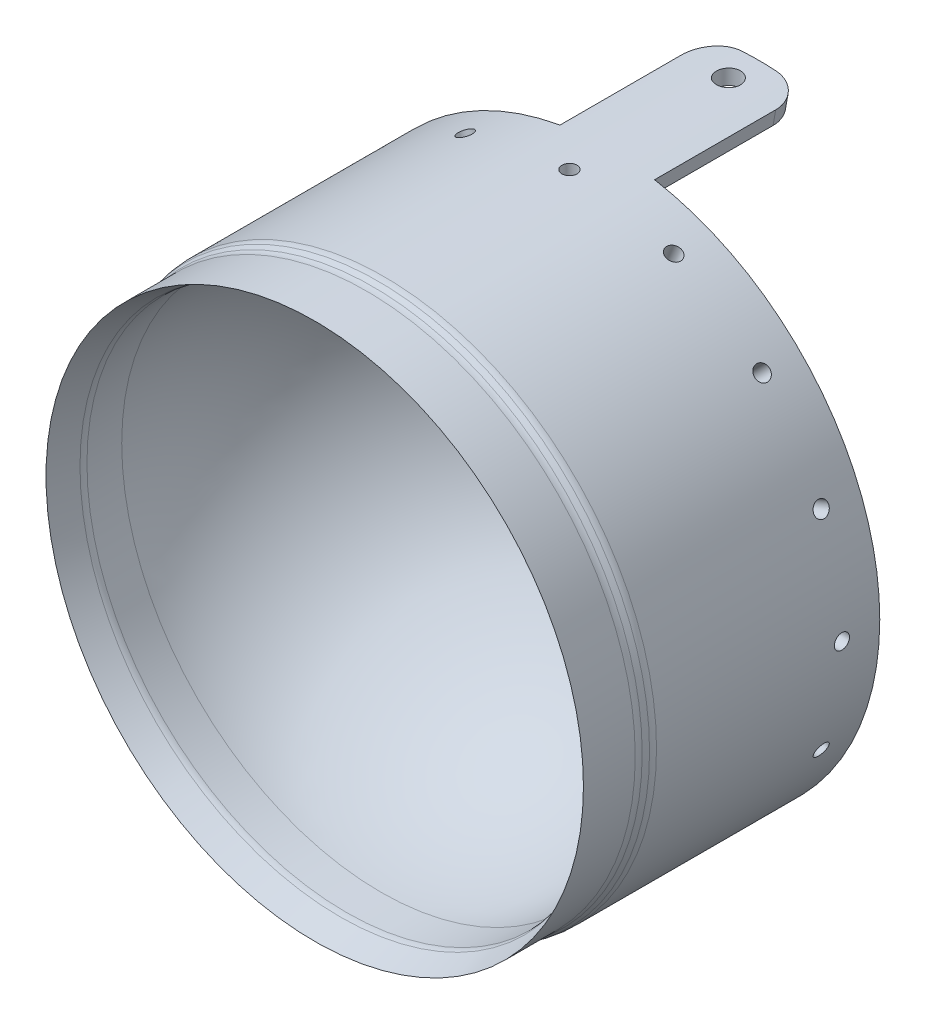
SolidWorks part; units mm, degrees
material "6061-T6 (SS)"
ref_plane "Front Plane" through (0, 0, 0) normal (0, 0, 1) x (1, 0, 0)
ref_plane "Top Plane" through (0, 0, 0) normal (0, 1, 0) x (1, 0, 0)
ref_plane "Right Plane" through (0, 0, 0) normal (1, 0, 0) x (0, 0, -1)
other "Center of Mass"
sketch "Sketch1" plane through (0, 0, 0) normal (0, 0, 1) x (1, 0, 0)
  circle A0 centre (0, 0) radius 72
  circle A1 centre (0, 0) radius 73
  dimension "D1" = 146
  dimension "D2" = 1
sketch "Sketch18" plane through (0, 0, 0) normal (0, 1, 0) x (1, 0, 0)
  line L0 (0, 0) -> (0, 72) construction
  line L1 (0, 72) -> (0, 68.5)
  line L2 (-72, 0) -> (-71, 0) construction
  line L9 (-71, 0) -> (-72, 0) construction
  line L11 (-72, 0) -> (72, 0) construction
  line L13 (-71, 0) -> (72, 0) construction
  line L16 (-73, 0) -> (73, 0) construction
  line L18 (-25, 72) -> (0, 72)
  line L22 (-72, 0) -> (73, 0) construction
  line L26 (-71, 0) -> (-71, -10) construction
  line L27 (-68.5, 0) -> (-68.5, -9.1886)
  line L29 (0, 72) -> (-25, 72) construction
  line L30 (-71.7434, -0.7698) -> (-71.2566, -2.2302)
  line L31 (-25, 67.5204) -> (-25, 72)
  line L36 (-71, -10) -> (-68.5, -10) construction
  line L38 (-72, 0) -> (0, 0) construction
  line L40 (-72, 0.8114) -> (-72, 59.7996)
  line L41 (-72, 59.7996) -> (-40.1, 59.7996)
  line L42 (-72, 49.7996) -> (-52, 49.7996) construction
  line L43 (-72, 39.7996) -> (-59.9999, 39.7996) construction
  line L44 (-71, -10) -> (-71, -3.8114)
  line L45 (-68.7566, -10.7698) -> (-71, -17.5)
  line L46 (-71, -17.5) -> (-71, -10)
  line L47 (-71, -3.8114) -> (-72, -3.8114) construction
  line L48 (-72, -3.8114) -> (-72, 0.8114) construction
  arc A8 (-72, 0) -> (0, 72) centre (0, 0) cw construction
  arc A9 (-68.5, 0) -> (0, 68.5) centre (0, 0) cw
  arc A10 (-40.1, 59.7996) -> (-25, 67.5204) centre (0, 0) cw
  arc A11 (-72, 0.8114) -> (-71.7434, -0.7698) centre (-67, 0.8114) ccw
  arc A12 (-71, -3.8114) -> (-71.2566, -2.2302) centre (-76, -3.8114) ccw
  arc A13 (-68.5, -9.1886) -> (-68.7566, -10.7698) centre (-73.5, -9.1886) cw
  point P28 (-71, -3)
  dimension "D12" = 5
  dimension "D13" = 5
  dimension "D14" = 5
  dimension "D1" = 2.5
  dimension "D2" = 10
  dimension "D3" = 3
  dimension "D4" = 25
  dimension "D5" = 7.5
  dimension "D6" = 10
  dimension "D7" = 12.2004
  dimension "D8" = 10
  dimension "D9" = 20
  dimension "D10" = 72
  dimension "D11" = 1
ref_axis "Axis1" through (0, 0, 0) along (0, 0, -1)
revolve "Revolve1" add sketch "Sketch18" angle 360 about axis through (0, 0, 0) along (0, 0, -1)
ref_plane "Plane24" through (0, 0, -72) normal (0, 0, -1) x (-1, 0, 0)
hole_wizard "Ø4.0 (4) Diameter Hole1" positions "3DSketch1" profile "Sketch23" hole size "Ø4.0" standard "ISO"
sketch3d "3DSketch1"
  line L0 (0, 0, -49.7996) -> (0, 72, -49.7996) construction
  circle A0 centre (0, 0, -49.7996) radius 72
  circle A1 centre (0, 0, -49.7996) radius 72 construction
  point P29 (0, 72, -49.7996)
  point P32 (0, 0, 22.2004)
  point P34 (0, 0, 22.2004)
  dimension "D1" = 10
sketch "Sketch23" plane through (0, 72, -49.7996) normal (1, 0, 0) x (0, 0, 1)
  line L0 (0, 0) -> (0, 16.3)
  line L1 (0, 16.3) -> (2, 14.3)
  line L2 (2, 14.3) -> (2, 0)
  line L5 (2, 0) -> (0, 0)
  line L10 (0, 16.3) -> (-2, 14.3) construction
  line L11 (0, -6.35) -> (0, 107.95) construction
  dimension "Hole Dia." = 4
  dimension "Hole Depth" = 14.3
  dimension "Drill Angle" = 90
pattern_circular "CirPattern1" count 16 over 360 about axis through (0, 0, 0) along (0, 0, -1) of "Ø4.0 (4) Diameter Hole1"
sketch "Sketch55" plane through (0, 0, -59.7996) normal (0, 0, -1) x (-1, 0, 0)
  circle A0 centre (0, 0) radius 2.175
  dimension "D1" = 4.35
fillet "Fillet9" radius 30 1 edges at (40.1, 0, -59.7996)
fillet "Fillet10" radius 25 1 edges at (25, 0, -67.5204)
extrude "Cut-Extrude37" cut sketch "Sketch55" along normal up to next
fillet "Fillet8" radius 3 1 edges at (2.175, 0, -68.4655)
sketch "Schizzo1" plane through (0, 0, -72) normal (0, 0, -1) x (-1, 0, 0)
  circle A0 centre (0, 0) radius 3.175
  circle A1 centre (0, 0) radius 2.175
  circle A2 centre (0, 0) radius 2.175 construction
  dimension "D1" = 6.35
extrude "Estrusione-Estrusione1" add sketch "Schizzo1" along normal blind 10
sketch "Schizzo2" plane through (0, 0, -59.7996) normal (0, 0, -1) x (-1, 0, 0)
  line L0 (0, 72) -> (0, 0) construction
  line L1 (-11.8081, 66.9669) -> (-12.5027, 70.9062)
  line L2 (12.5027, 70.9062) -> (11.8081, 66.9669)
  circle A1 centre (0, 0) radius 68
  circle A3 centre (0, 0) radius 72 construction
  circle A4 centre (0, 0) radius 72
  dimension "D1" = 136
  dimension "D2" = 10
extrude "Estrusione-Estrusione2" add sketch "Schizzo2" along normal blind 40 contours L0 A1 L2 | L0 L1 A1 region at (0, 69.6641, -59.7996)
fillet "Raccordo1" radius 8 2 edges at (12.1554, 68.9365, -99.7996) (-12.1554, 68.9365, -99.7996)
sketch "Sketch56" plane through (0, 0, 0) normal (0, 1, 0) x (1, 0, 0)
  line L0 (3.8476, 99.7996) -> (-3.8476, 99.7996) construction
  line L1 (3.8476, 99.7996) -> (-3.8476, 99.7996) construction
  line L2 (11.8081, 91.7996) -> (11.8081, 59.7996) construction
  line L3 (11.8081, 91.7996) -> (11.8081, 59.7996) construction
  line L4 (-11.8081, 91.7996) -> (-11.8081, 59.7996) construction
  line L5 (-11.8081, 91.7996) -> (-11.8081, 59.7996) construction
  line L6 (-11.8081, 91.7996) -> (0, 91.7996) construction
  line L7 (0, 91.7996) -> (0, 99.7996) construction
  circle A0 centre (0, 91.7996) radius 3.175
  dimension "D1" = 6.35
extrude "Cut-Extrude38" cut sketch "Sketch56" along normal up to next contours A0
